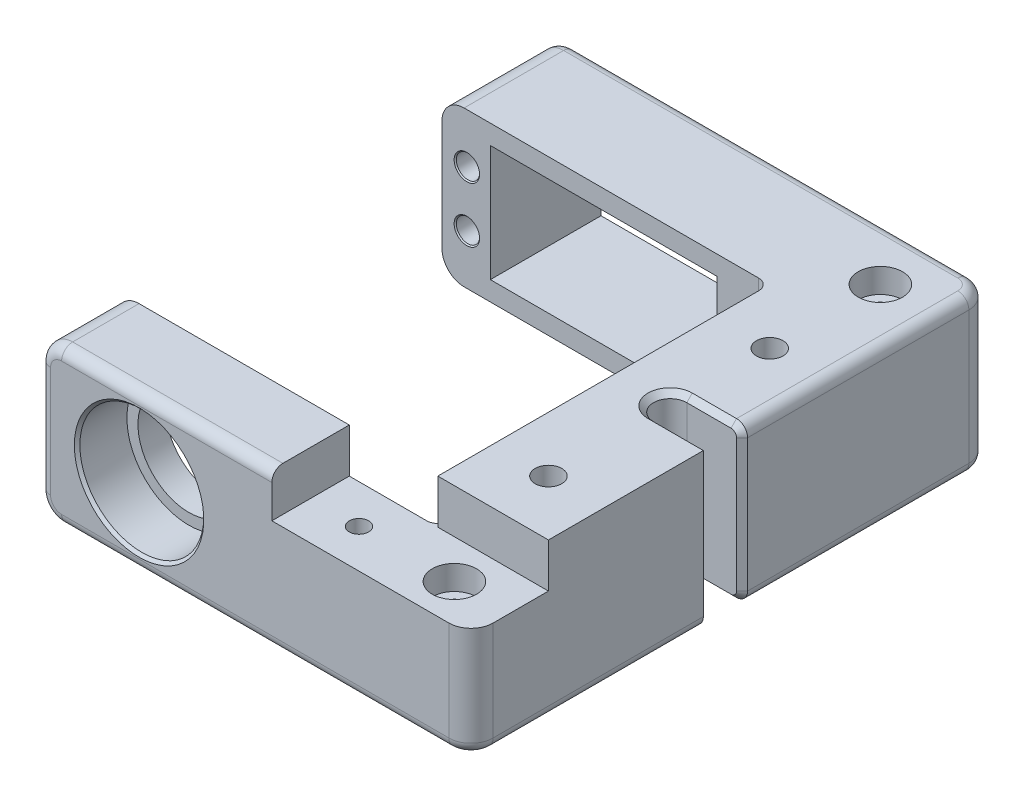
SolidWorks part; units mm, degrees
ref_plane "Top Plane" through (0, 0, 0) normal (0, 0, 1) x (1, 0, 0)
ref_plane "Right Plane" through (0, 0, 0) normal (0, 1, 0) x (1, 0, 0)
ref_plane "Front Plane" through (0, 0, 0) normal (1, 0, 0) x (0, 0, -1)
sketch "Sketch1" plane through (0, 0, 0) normal (0, 0, 1) x (1, 0, 0)
  line L0 (-10, 0) -> (30, 0) construction
  line L1 (-10, 10) -> (30, 10) construction
  line L2 (-10, 10) -> (-10, -10) construction
  line L3 (-10, -10) -> (30, -10) construction
  line L4 (30, 10) -> (30, -10) construction
  line L5 (-10, 10) -> (-17.25, 10) construction
  line L6 (-17.25, 10) -> (-17.25, -10) construction
  line L7 (-17.25, -10) -> (-10, -10) construction
  line L8 (10, 10) -> (10, -10) construction
  line L9 (37.25, -10) -> (30, -10) construction
  line L10 (37.25, 10) -> (37.25, -10) construction
  line L11 (30, 10) -> (37.25, 10) construction
  line L12 (40, 14) -> (40, -14) construction
  line L13 (-19.25, 14) -> (60, 14)
  line L14 (-19.25, 14) -> (-19.25, -14)
  line L15 (-19.25, -14) -> (60, -14)
  line L16 (60, 14) -> (60, -14)
  circle A0 centre (0, 0) radius 11 construction
  circle A1 centre (0, 0) radius 4 construction
  circle A2 centre (-14.75, 5) radius 2 construction
  circle A3 centre (-14.75, -5) radius 2 construction
  circle A4 centre (34.75, -5) radius 2 construction
  circle A5 centre (34.75, 5) radius 2 construction
  dimension "D1" = 22
  dimension "D2" = 8
  dimension "D12" = 4
  dimension "D3" = 40
  dimension "D4" = 20
  dimension "D5" = 54.5
  dimension "D6" = 37.25
  dimension "D7" = 20
  dimension "D8" = 40
  dimension "D9" = 14
  dimension "D10" = 14
  dimension "D11" = 2
  dimension "D13" = 10
  dimension "D14" = 49.5
extrude "Boss-Extrude1" add sketch "Sketch1" along normal blind 20
sketch "Sketch2" plane through (0, 0, 20) normal (0, 0, 1) x (1, 0, 0)
  line L1 (40, 14) -> (60, 14)
  line L2 (40, 14) -> (40, -14)
  line L3 (40, -14) -> (60, -14)
  line L4 (60, 14) -> (60, -14)
extrude "Boss-Extrude2" add sketch "Sketch2" along normal blind 60
sketch "Sketch3" plane through (0, 0, 80) normal (0, 0, 1) x (1, 0, 0)
  line L0 (-19.25, -14) -> (60, -14) construction
  line L1 (60, 14) -> (-18, 14)
  line L2 (60, 14) -> (60, -14)
  line L3 (60, -14) -> (-18, -14)
  line L4 (-18, 14) -> (-18, -14)
  dimension "D1" = 18
extrude "Boss-Extrude3" add sketch "Sketch3" along normal blind 14
sketch "Sketch4" plane through (0, 0, 20) normal (0, 0, 1) x (1, 0, 0)
  line L8 (-10.5, -10.5) -> (30.5, -10.5)
  line L9 (30.5, -10.5) -> (30.5, 10.5)
  line L10 (30.5, 10.5) -> (-10.5, 10.5)
  line L11 (-10.5, 10.5) -> (-10.5, -10.5)
  line L12 (-10.5, -10.5) -> (30.5, -10.5)
  line L13 (30.5, -10.5) -> (30.5, 10.5)
  line L14 (30.5, 10.5) -> (-10.5, 10.5)
  line L15 (-10.5, 10.5) -> (-10.5, -10.5)
  dimension "D1" = 0.5
extrude "Cut-Extrude1" cut sketch "Sketch4" against normal through all
sketch "Sketch5" plane through (0, 0, 20) normal (0, 0, 1) x (1, 0, 0)
  circle A4 centre (34.75, -5) radius 2.1
  circle A5 centre (34.75, 5) radius 2.1
  circle A6 centre (-14.75, -5) radius 2.1
  circle A7 centre (-14.75, 5) radius 2.1
  point P1 (0, 0)
  point P3 (0, 0)
  point P5 (0, 0)
  point P7 (0, 0)
  point P13 (-13.5072, 4.7881)
  dimension "D1" = 4.2
extrude "Cut-Extrude2" cut sketch "Sketch5" against normal through all
sketch "Sketch6" plane through (0, 0, 0) normal (0, 0, -1) x (-1, 0, 0)
  line L0 (-10, 10.5) -> (-10, -10.5) construction
  line L1 (-34.75, 9.0126) -> (-38.225, 7.0063)
  line L2 (-38.225, 7.0063) -> (-38.225, 2.9937)
  line L3 (-38.225, 2.9937) -> (-34.75, 0.9874)
  line L4 (-34.75, 0.9874) -> (-31.275, 2.9937)
  line L5 (-31.275, 2.9937) -> (-31.275, 7.0063)
  line L6 (-31.275, 7.0063) -> (-34.75, 9.0126)
  line L7 (-34.75, -0.9874) -> (-38.225, -2.9937)
  line L8 (-38.225, -2.9937) -> (-38.225, -7.0063)
  line L9 (-38.225, -7.0063) -> (-34.75, -9.0126)
  line L10 (-34.75, -9.0126) -> (-31.275, -7.0063)
  line L11 (-31.275, -7.0063) -> (-31.275, -2.9937)
  line L12 (-31.275, -2.9937) -> (-34.75, -0.9874)
  line L13 (-30.5, 10.5) -> (10.5, 10.5) construction
  line L14 (10.5, -10.5) -> (-30.5, -10.5) construction
  line L15 (11.275, -2.9937) -> (14.75, -0.9874)
  line L16 (11.275, -7.0063) -> (11.275, -2.9937)
  line L17 (14.75, -9.0126) -> (11.275, -7.0063)
  line L18 (18.225, -7.0063) -> (14.75, -9.0126)
  line L19 (18.225, -2.9937) -> (18.225, -7.0063)
  line L20 (14.75, -0.9874) -> (18.225, -2.9937)
  line L21 (11.275, 7.0063) -> (14.75, 9.0126)
  line L22 (11.275, 2.9937) -> (11.275, 7.0063)
  line L23 (14.75, 0.9874) -> (11.275, 2.9937)
  line L24 (18.225, 2.9937) -> (14.75, 0.9874)
  line L25 (18.225, 7.0063) -> (18.225, 2.9937)
  line L26 (14.75, 9.0126) -> (18.225, 7.0063)
  circle A0 centre (-34.75, 5) radius 3.475 construction
  circle A1 centre (-34.75, -5) radius 3.475 construction
  circle A2 centre (14.75, -5) radius 3.475 construction
  circle A3 centre (14.75, 5) radius 3.475 construction
  dimension "D1" = 6.95
extrude "Cut-Extrude3" cut sketch "Sketch6" against normal offset from surface (4 mm away) 16 up to face at (36.85, 5, 20)
sketch "Sketch7" plane through (0, 0, 94) normal (0, 0, 1) x (1, 0, 0)
  circle A2 centre (0, 0) radius 11.2
  circle A3 centre (0, 0) radius 11.2
  dimension "D1" = 0.2
extrude "Cut-Extrude4" cut sketch "Sketch7" against normal blind 9
sketch "Sketch8" plane through (0, 0, 85) normal (0, 0, 1) x (1, 0, 0)
  circle A0 centre (0, 0) radius 9.2
  circle A1 centre (0, 0) radius 11.2 construction
  dimension "D1" = 2
extrude "Cut-Extrude5" cut sketch "Sketch8" against normal up to next
sketch "Sketch12" plane through (0, 14, 0) normal (0, 1, 0) x (1, 0, 0)
  line L0 (60, 0) -> (-19.25, 0) construction
  line L1 (60, -94) -> (60, 0) construction
  line L3 (35.6842, -80) -> (35.6842, -94) construction
  line L4 (40, -80) -> (-18, -80) construction
  line L5 (60, -94) -> (-18, -94) construction
  line L6 (35.6842, -87) -> (50, -87) construction
  circle A0 centre (50, -10) radius 2 construction
  circle A1 centre (50, -10) radius 3.75 construction
  circle A2 centre (50, -87) radius 2 construction
  circle A3 centre (50, -87) radius 3.75 construction
  dimension "D1" = 4
  dimension "D2" = 7.5
  dimension "D3" = 10
  dimension "D4" = 10
  dimension "D6" = 10
sketch "Sketch15" plane through (0, 14, 0) normal (0, 1, 0) x (1, 0, 0)
  line L0 (32.75, -87) -> (50, -87) construction
  circle A0 centre (32.75, -87) radius 1.75
  dimension "D1" = 17.25
  dimension "D2" = 3.5
extrude "Cut-Extrude6" cut sketch "Sketch15" against normal through all
sketch "Sketch16" plane through (0, -14, 0) normal (0, -1, 0) x (1, 0, 0)
  line L1 (31.1479, 89.775) -> (29.5457, 87)
  line L2 (29.5457, 87) -> (31.1479, 84.225)
  line L3 (31.1479, 84.225) -> (34.3521, 84.225)
  line L4 (34.3521, 84.225) -> (35.9543, 87)
  line L5 (35.9543, 87) -> (34.3521, 89.775)
  line L6 (34.3521, 89.775) -> (31.1479, 89.775)
  circle A0 centre (32.75, 87) radius 2.775 construction
  dimension "D1" = 5.55
extrude "Cut-Extrude7" cut sketch "Sketch16" against normal blind 5
sketch "Sketch17" plane through (0, 14, 0) normal (0, 1, 0) x (1, 0, 0)
  line L0 (50, -10) -> (50, -87) construction
  line L1 (50, -45) -> (60, -45)
  line L2 (60, -94) -> (60, 0) construction
  line L3 (50, -51) -> (60, -51)
  line L4 (60, -45) -> (60, -51)
  arc A0 (50, -45) -> (50, -51) centre (50, -48) ccw
  dimension "D1" = 6
  dimension "D2" = 38
extrude "Cut-Extrude8" cut sketch "Sketch17" against normal through all
sketch "Sketch18" plane through (0, 14, 0) normal (0, 1, 0) x (1, 0, 0)
  line L0 (40, -80) -> (-18, -80) construction
  line L1 (24, -80) -> (60, -80)
  line L2 (24, -80) -> (24, -94)
  line L3 (24, -94) -> (60, -94)
  line L4 (60, -80) -> (60, -94)
  dimension "D1" = 36
extrude "Cut-Extrude9" cut sketch "Sketch18" against normal blind 8
hole_wizard "CBORE for M4 Hex Socket Head Cap Screw1" positions "Sketch13" profile "Sketch14" counterbore size "M4" standard "ISO" end condition through all
sketch "Sketch13" plane through (0, 14, 0) normal (0, 1, 0) x (1, 0, 0)
  point P2 (50, -10)
sketch "Sketch14" plane through (50, 14, 10) normal (1, 0, 0) x (0, 0, 1)
  line L0 (0, 0) -> (0, 28)
  line L1 (0, 28) -> (2.1, 28)
  line L3 (2.1, 28) -> (2.1, 4.4)
  line L4 (2.1, 4.4) -> (4, 4.4)
  line L5 (4, 4.4) -> (4, 0)
  line L7 (4, 0) -> (0, 0)
  line L11 (0, -6.35) -> (0, 107.95) construction
  dimension "Thru Hole Dia." = 4.2
  dimension "Thru Hole Depth" = 28
  dimension "C'Bore Dia." = 8
  dimension "C'Bore Depth" = 4.4
hole_wizard "CBORE for M4 Hex Socket Head Cap Screw2" positions "Sketch19" profile "Sketch20" counterbore size "M4" standard "ISO" end condition through all
sketch "Sketch19" plane through (0, 6, 0) normal (0, 1, 0) x (1, 0, 0)
  point P0 (50, -87)
sketch "Sketch20" plane through (50, 6, 87) normal (1, 0, 0) x (0, 0, 1)
  line L0 (0, 0) -> (0, 20)
  line L1 (0, 20) -> (2.1, 20)
  line L3 (2.1, 20) -> (2.1, 4.4)
  line L4 (2.1, 4.4) -> (4, 4.4)
  line L5 (4, 4.4) -> (4, 0)
  line L7 (4, 0) -> (0, 0)
  line L11 (0, -6.35) -> (0, 107.95) construction
  dimension "Thru Hole Dia." = 4.2
  dimension "Thru Hole Depth" = 20
  dimension "C'Bore Dia." = 8
  dimension "C'Bore Depth" = 4.4
sketch "Sketch22" plane through (0, 14, 0) normal (0, 1, 0) x (1, 0, 0)
  line L0 (40, -50) -> (60, -50) construction
  line L1 (40, -80) -> (40, -20) construction
  line L2 (60, -45) -> (60, 0) construction
  line L3 (50, -30) -> (50, -70) construction
  circle A0 centre (50, -30) radius 2.4
  circle A1 centre (50, -70) radius 2.4
  point P10 (50, -50)
  dimension "D1" = 40
  dimension "D2" = 4.8
extrude "Cut-Extrude10" cut sketch "Sketch22" against normal through all
fillet "Fillet6" radius 0.2 7 edges at (32.75, -9, 85.25) (30.3468, -9, 85.6125) (32.75, -9, 84.225) (35.1532, -9, 85.6125) (35.1532, -9, 88.3875) (32.75, -9, 89.775) (30.3468, -9, 88.3875)
fillet "Fillet1" radius 4 4 edges at (-18, -14, 87) (-18, 14, 87) (-19.25, -14, 10) (-19.25, 14, 10)
fillet "Fillet3" radius 4 2 edges at (60, 0, 0) (60, -4, 94)
fillet "Fillet4" radius 2 2 edges at (40, 0, 20) (40, -4, 80)
fillet "Fillet5" radius 2 16 edges at (58.8284, -14, 92.8284) (21, -14, 94) (-16.8284, -12.8284, 94) (-18, 0, 94) (-16.8284, 12.8284, 94) (5, 14, 94) (60, 14, 24.5) (58.8284, 14, 1.1716) (20.375, 14, 0) (-18.0784, 12.8284, 0) (-19.25, 0, 0) (-18.0784, -12.8284, 0) (20.375, -14, 0) (58.8284, -14, 1.1716) (60, -14, 24.5) (60, -14, 70.5)
chamfer "Chamfer1" distance 0.5 angle 45 1 edges at (11.2, 0, 94)
chamfer "Chamfer2" distance 1 angle 45 11 edges at (47, 14, 48) (47, -14, 48) (54, -14, 45) (54, -14, 51) (59.4142, -13.4142, 51) (60, 1, 51) (54, 14, 45) (55, 14, 51) (59.4142, -13.4142, 45) (60, 0, 45) (59.4142, 13.4142, 45)
chamfer "Chamfer3" distance 0.2 angle 45 4 edges at (36.85, 5, 20) (36.85, -5, 20) (-12.65, -5, 20) (-12.65, 5, 20)
chamfer "Chamfer4" distance 0.2 angle 45 2 edges at (50, 9.6, 12.1) (50, 1.6, 89.1)
